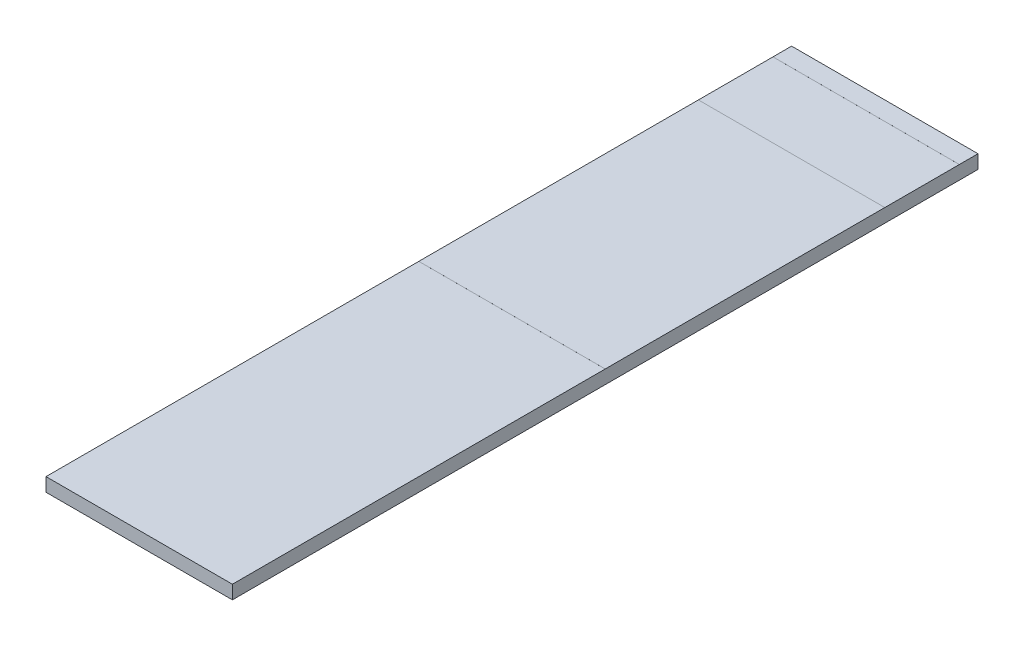
SolidWorks part; units mm, degrees
ref_plane "Top Plane" through (0, 0, 0) normal (0, 0, 1) x (1, 0, 0)
ref_plane "Front Plane" through (0, 0, 0) normal (0, 1, 0) x (1, 0, 0)
ref_plane "Right Plane" through (0, 0, 0) normal (1, 0, 0) x (0, 0, -1)
sketch "Sketch1" plane through (0, 0, 0) normal (0, 0, 1) x (1, 0, 0)
  line L1 (0, 0) -> (1, 0)
  line L2 (0, 0) -> (0, 0.0729)
  line L3 (0, 0.0729) -> (1, 0.0729)
  line L4 (1, 0) -> (1, 0.0729)
  dimension "D1" = 0.0729
  dimension "D2" = 1
extrude "Boss-Extrude1" add sketch "Sketch1" along normal blind 4 contours L3 L4 L1 L2
sketch "Sketch7" plane through (0, 0.0729, 0) normal (0, 1, 0) x (1, 0, 0)
  line L0 (0, -4) -> (0, 0) construction
  line L1 (1, 0) -> (0, 0)
  line L2 (1, 0) -> (1, -0.1)
  line L3 (1, -0.1) -> (0, -0.1)
  line L4 (0, 0) -> (0, -0.1)
  line L5 (1, -4) -> (1, 0) construction
  line L6 (1, -0.5) -> (0, -0.5)
  line L7 (1, -0.5) -> (1, -2)
  line L8 (1, -2) -> (0, -2)
  line L9 (0, -0.5) -> (0, -2)
  point P13 (0, -0.5)
  dimension "D1" = 0.1
  dimension "D2" = 0.5
  dimension "D3" = 2
extrude "Boss-Extrude6" add sketch "Sketch7" along normal blind 0.0001
extrude "Boss-Extrude7" add sketch "Sketch7<2>" against normal blind 0.0001 from vertex starting at point (0, 0, 0)
sketch "Sketch7<2>" plane through (0, 0.0729, 0) normal (0, 1, 0) x (1, 0, 0) same geometry as "Sketch7"
